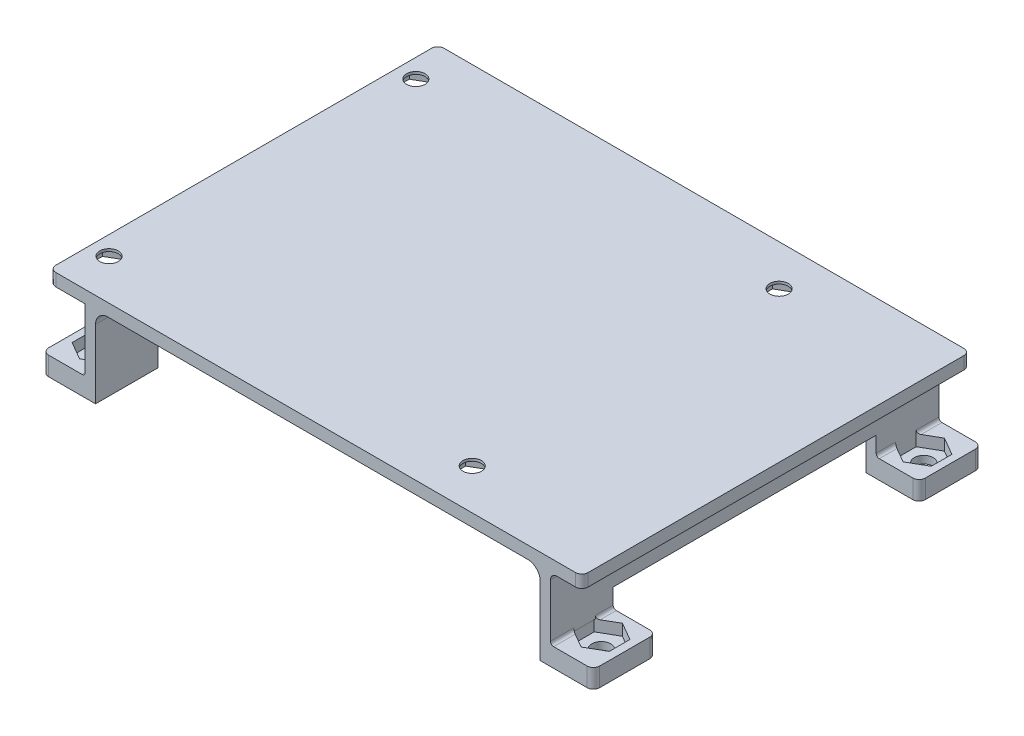
SolidWorks part; units mm, degrees
ref_plane "前基準面" through (0, 0, 0) normal (0, 0, 1) x (1, 0, 0)
ref_plane "上基準面" through (0, 0, 0) normal (0, 1, 0) x (1, 0, 0)
ref_plane "右基準面" through (0, 0, 0) normal (1, 0, 0) x (0, 0, -1)
sketch "草圖1" plane through (0, 0, 0) normal (0, 0, 1) x (1, 0, 0)
  line L0 (-133.4262, 0) -> (6537.8852, 0) construction
  line L1 (0, -133.4262) -> (0, 6537.8852) construction
  line L2 (-44, 0) -> (-44, 3)
  line L3 (-44, 3) -> (-37.15, 3)
  line L4 (-37.15, 3) -> (-37.15, 13)
  line L6 (37.15, 13) -> (37.15, 3)
  line L7 (37.15, 3) -> (44, 3)
  line L8 (44, 3) -> (44, 0)
  line L10 (-35.5, 0) -> (-35.5, 13)
  line L11 (-35.5, 13) -> (35.5, 13)
  line L12 (35.5, 13) -> (35.5, 0)
  line L13 (-44, 0) -> (-35.5, 0)
  line L14 (35.5, 0) -> (44, 0)
  line L16 (-42.85, 15) -> (-42.85, 13)
  line L17 (-37.15, 13) -> (-42.85, 13)
  line L18 (-42.85, 15) -> (42.15, 15)
  line L19 (42.15, 15) -> (42.15, 13)
  line L20 (42.15, 13) -> (37.15, 13)
  dimension "D1" = 1.65
  dimension "D2" = 13
  dimension "D3" = 71
  dimension "D4" = 88
  dimension "D5" = 2
  dimension "D6" = 3
  dimension "D7" = 85
  dimension "D8" = 5.7
extrude "填料-伸長1" add sketch "草圖1" along normal mid plane 62
sketch "草圖2" plane through (0, 0, 0) normal (1, 0, 0) x (0, 0, -1)
  line L0 (-1000, 0) -> (49000, 0) construction
  line L1 (0, -1000) -> (0, 49000) construction
  line L3 (-21, -6) -> (21, -6)
  line L4 (-21, -6) -> (-21, 6)
  line L5 (-21, 6) -> (21, 6)
  line L6 (21, -6) -> (21, 6)
  line L7 (-21, -6) -> (21, 6) construction
  line L8 (-21, 6) -> (21, -6) construction
  point P4 (0, 0)
  dimension "D1" = 42
  dimension "D2" = 12
extrude "除料-伸長1" cut sketch "草圖2" against normal through all both and the other way through all
sketch "草圖3" plane through (0, 0, 0) normal (0, 1, 0) x (1, 0, 0)
  line L0 (-40, -1017.5) -> (-40, 48982.5) construction
  line L2 (40, -1017.5) -> (40, 48982.5) construction
  line L4 (-1031.5, 25.75) -> (48968.5, 25.75) construction
  line L5 (0, -1000) -> (0, 49000) construction
  line L6 (-1031.5, -25.75) -> (48968.5, -25.75) construction
  line L8 (-1000, 0) -> (49000, 0) construction
  line L9 (-42.85, -31) -> (-37.15, -31) construction
  line L10 (35.5, -31) -> (44, -31) construction
  circle A0 centre (-40, 25.75) radius 1.5
  circle A1 centre (40, 25.75) radius 1.5
  circle A2 centre (40, -25.75) radius 1.5
  circle A3 centre (-40, -25.75) radius 1.5
  point P12 (-40, -31)
  point P16 (40, -31)
  dimension "D1" = 3
  dimension "D2" = 51.5
  dimension "D3" = 80
extrude "除料-伸長4" cut sketch "草圖3" along normal up to next contours A0 | A1 | A3 | A2
sketch "草圖5" plane through (0, 15, 0) normal (0, 1, 0) x (1, 0, 0)
  line L0 (-1000, 0) -> (49000, 0) construction
  line L1 (-1033.1907, 24.5) -> (48966.8093, 24.5) construction
  line L2 (-1033.1907, -24.5) -> (48966.8093, -24.5) construction
  line L3 (-39.85, 24.5) -> (-39.85, -24.5) construction
  line L4 (18.15, 24.5) -> (18.15, -24.5) construction
  line L5 (-42.85, -31) -> (-42.85, 31) construction
  circle A0 centre (-39.85, 24.5) radius 1.475
  circle A1 centre (-39.85, -24.5) radius 1.475
  circle A2 centre (18.15, 24.5) radius 1.475
  circle A3 centre (18.15, -24.5) radius 1.475
  dimension "D3" = 2.95
  dimension "D1" = 49
  dimension "D2" = 24.5
  dimension "D4" = 58
  dimension "D5" = 3
extrude "除料-伸長5" cut sketch "草圖5" against normal blind 5
ref_plane "平面1" through (0, 3, 0) normal (0, 1, 0) x (1, 0, 0)
sketch "草圖17" plane through (0, 13, 0) normal (0, -1, 0) x (1, 0, 0)
  line L7 (20.65, 23.0566) -> (20.65, 25.9434)
  line L8 (20.65, 25.9434) -> (18.15, 27.3868)
  line L9 (18.15, 27.3868) -> (15.65, 25.9434)
  line L10 (15.65, 25.9434) -> (15.65, 23.0566)
  line L11 (15.65, 23.0566) -> (18.15, 21.6132)
  line L12 (18.15, 21.6132) -> (20.65, 23.0566)
  line L13 (20.65, -25.9434) -> (20.65, -23.0566)
  line L14 (20.65, -23.0566) -> (18.15, -21.6132)
  line L15 (18.15, -21.6132) -> (15.65, -23.0566)
  line L16 (15.65, -23.0566) -> (15.65, -25.9434)
  line L17 (15.65, -25.9434) -> (18.15, -27.3868)
  line L18 (18.15, -27.3868) -> (20.65, -25.9434)
  line L19 (-39.85, 21.6132) -> (-37.35, 23.0566)
  line L20 (-37.35, 23.0566) -> (-37.35, 25.9434)
  line L21 (-37.35, 25.9434) -> (-39.85, 27.3868)
  line L22 (-39.85, 27.3868) -> (-42.35, 25.9434)
  line L23 (-42.35, 25.9434) -> (-42.35, 23.0566)
  line L24 (-42.35, 23.0566) -> (-39.85, 21.6132)
  line L26 (-39.85, -27.3868) -> (-37.35, -25.9434)
  line L27 (-37.35, -25.9434) -> (-37.35, -23.0566)
  line L28 (-37.35, -23.0566) -> (-39.85, -21.6132)
  line L29 (-39.85, -21.6132) -> (-42.35, -23.0566)
  line L30 (-42.35, -23.0566) -> (-42.35, -25.9434)
  line L31 (-42.35, -25.9434) -> (-39.85, -27.3868)
  circle A0 centre (18.15, 24.5) radius 2.5 construction
  circle A1 centre (18.15, -24.5) radius 2.5 construction
  circle A2 centre (-39.85, 24.5) radius 2.5 construction
  circle A3 centre (-39.85, -24.5) radius 2.5 construction
  dimension "D1" = 5
  dimension "D2" = 5
  dimension "D3" = 5
  dimension "D4" = 5
extrude "除料-伸長8" cut sketch "草圖17" against normal blind 1.6
fillet "圓角1" radius 1 12 edges at (42.15, 14, -31) (44, 1.5, -31) (44, 1.5, -21) (44, 1.5, 21) (44, 1.5, 31) (42.15, 14, 31) (-42.85, 14, -31) (-44, 1.5, -31) (-44, 1.5, -21) (-44, 1.5, 21) (-44, 1.5, 31) (-42.85, 14, 31)
fillet "圓角7" radius 2 2 edges at (35.5, 13, 0) (-35.5, 13, 0)
sketch "草圖19" plane through (0, 3, 0) normal (0, 1, 0) x (1, 0, 0)
  line L1 (-40, -29.0409) -> (-37.15, -27.3954)
  line L2 (-37.15, -27.3954) -> (-37.15, -24.1046)
  line L3 (-37.15, -24.1046) -> (-40, -22.4591)
  line L4 (-40, -22.4591) -> (-42.85, -24.1046)
  line L5 (-42.85, -24.1046) -> (-42.85, -27.3954)
  line L6 (-42.85, -27.3954) -> (-40, -29.0409)
  line L7 (39.8961, -28.8509) -> (42.7461, -27.2055)
  line L8 (42.7461, -27.2055) -> (42.7461, -23.9146)
  line L9 (42.7461, -23.9146) -> (39.8961, -22.2691)
  line L10 (39.8961, -22.2691) -> (37.0461, -23.9146)
  line L11 (37.0461, -23.9146) -> (37.0461, -27.2055)
  line L12 (37.0461, -27.2055) -> (39.8961, -28.8509)
  line L13 (42.85, 24.1046) -> (42.85, 27.3954)
  line L14 (42.85, 27.3954) -> (40, 29.0409)
  line L15 (40, 29.0409) -> (37.15, 27.3954)
  line L16 (37.15, 27.3954) -> (37.15, 24.1046)
  line L17 (37.15, 24.1046) -> (40, 22.4591)
  line L18 (40, 22.4591) -> (42.85, 24.1046)
  line L19 (-40, 22.4591) -> (-37.15, 24.1046)
  line L20 (-37.15, 24.1046) -> (-37.15, 27.3954)
  line L21 (-37.15, 27.3954) -> (-40, 29.0409)
  line L22 (-40, 29.0409) -> (-42.85, 27.3954)
  line L23 (-42.85, 27.3954) -> (-42.85, 24.1046)
  line L24 (-42.85, 24.1046) -> (-40, 22.4591)
  circle A0 centre (-40, -25.75) radius 2.85 construction
  circle A1 centre (39.8961, -25.56) radius 2.85 construction
  circle A2 centre (40, 25.75) radius 2.85 construction
  circle A3 centre (-40, 25.75) radius 2.85 construction
  dimension "D1" = 5.7
  dimension "D2" = 5.7
  dimension "D3" = 5.7
  dimension "D4" = 5.7
extrude "除料-伸長9" cut sketch "草圖19" against normal blind 1.8
fillet "圓角5" radius 0.5 8 edges at (37.15, 3, -22.5523) (37.15, 3, -29.1977) (37.15, 3, 29.1327) (37.15, 3, 22.4273) (-37.15, 3, -22.5523) (-37.15, 3, -29.1977) (-37.15, 3, 22.5523) (-37.15, 3, 29.1977)
fillet "圓角8" radius 1 1 edges at (37.15, 13, 0)
